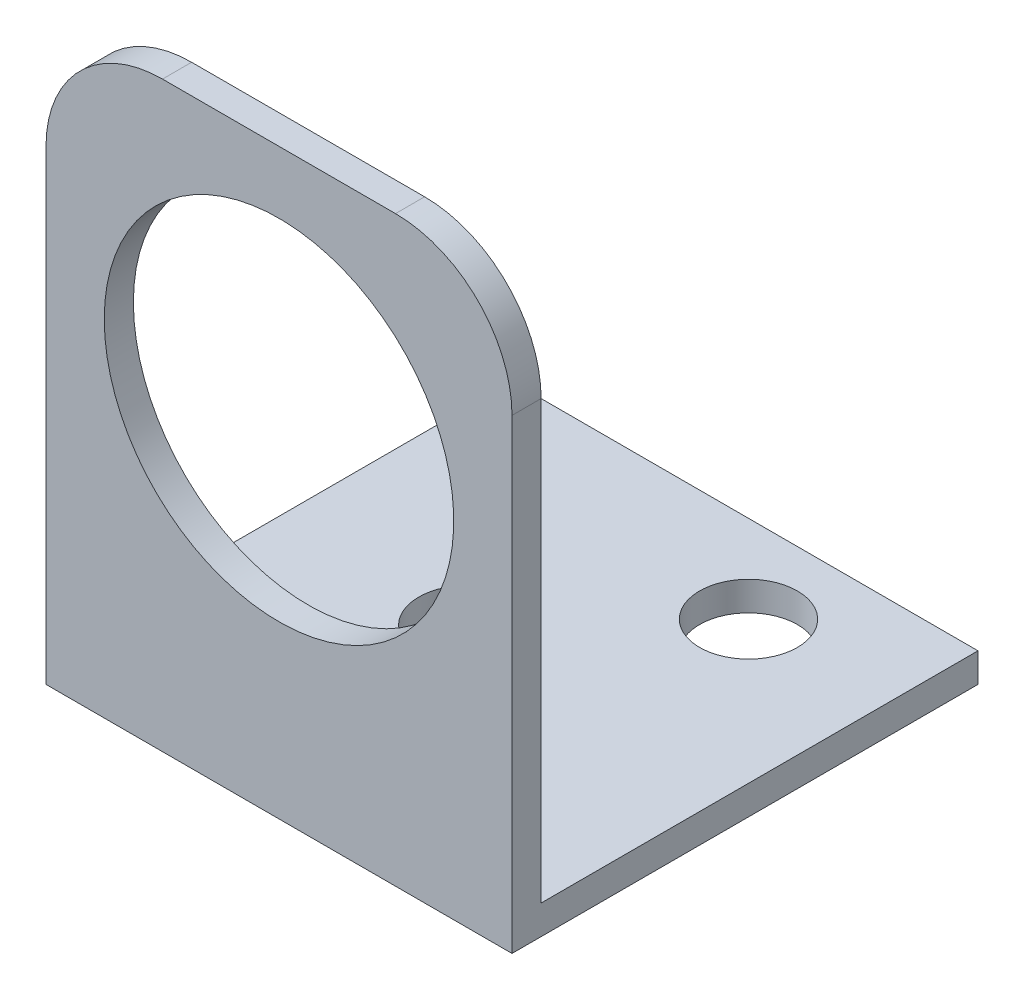
SolidWorks part; units mm, degrees
material "6061-T6 (SS)"
ref_plane "Front" through (0, 0, 0) normal (0, 0, 1) x (1, 0, 0)
ref_plane "Top" through (0, 0, 0) normal (0, 1, 0) x (1, 0, 0)
ref_plane "Right" through (0, 0, 0) normal (1, 0, 0) x (0, 0, -1)
sketch "Sketch1" plane through (0, 0, 0) normal (1, 0, 0) x (0, 0, -1)
  line L0 (1.5875, 1.5875) -> (25.4, 1.5875)
  line L1 (0, 0) -> (25.4, 0)
  line L2 (0, 0) -> (0, 31.75)
  line L5 (1.5875, 1.5875) -> (1.5875, 31.75)
  line L6 (25.4, 0) -> (25.4, 1.5875)
  line L7 (0, 31.75) -> (1.5875, 31.75)
  dimension "D1" = 31.75
  dimension "D2" = 25.4
  dimension "D3" = 1.5875
extrude "Boss-Extrude1" add sketch "Sketch1" along normal blind 25.4
sketch "Sketch2" plane through (0, 0, -1.5875) normal (0, 0, -1) x (-1, 0, 0)
  circle A0 centre (-12.7, 18.8307) radius 9.525 construction
  circle A1 centre (-12.7, 18.8307) radius 9.525
extrude "Cut-Extrude1" cut sketch "Sketch2" against normal up to next
fillet "Fillet1" radius 6.35 2 edges at (25.4, 31.75, -0.7937) (0, 31.75, -0.7937)
sketch "Sketch3" plane through (0, 0, 0) normal (0, -1, 0) x (1, 0, 0)
  line L1 (17.653, -20.6375) -> (17.653, -25.4) construction
  line L2 (25.4, -25.4) -> (0, -25.4) construction
  line L4 (10.287, -12.7) -> (10.287, -25.4) construction
  line L5 (7.62, 4.3539) -> (7.62, -55.9711) construction
  line L6 (20.32, 4.3539) -> (20.32, -55.9711) construction
  circle A0 centre (17.653, -20.6375) radius 2.667
  circle A1 centre (10.287, -12.7) radius 2.667
  point P9 (11.6426, -12.7)
  point P11 (7.747, -12.7)
  point P13 (7.747, -12.7)
  point P14 (10.2634, -12.7)
  dimension "D1" = 5.334
  dimension "D3" = 12.7
  dimension "D2" = 4.7625
extrude "Cut-Extrude2" cut sketch "Sketch3" against normal up to next
